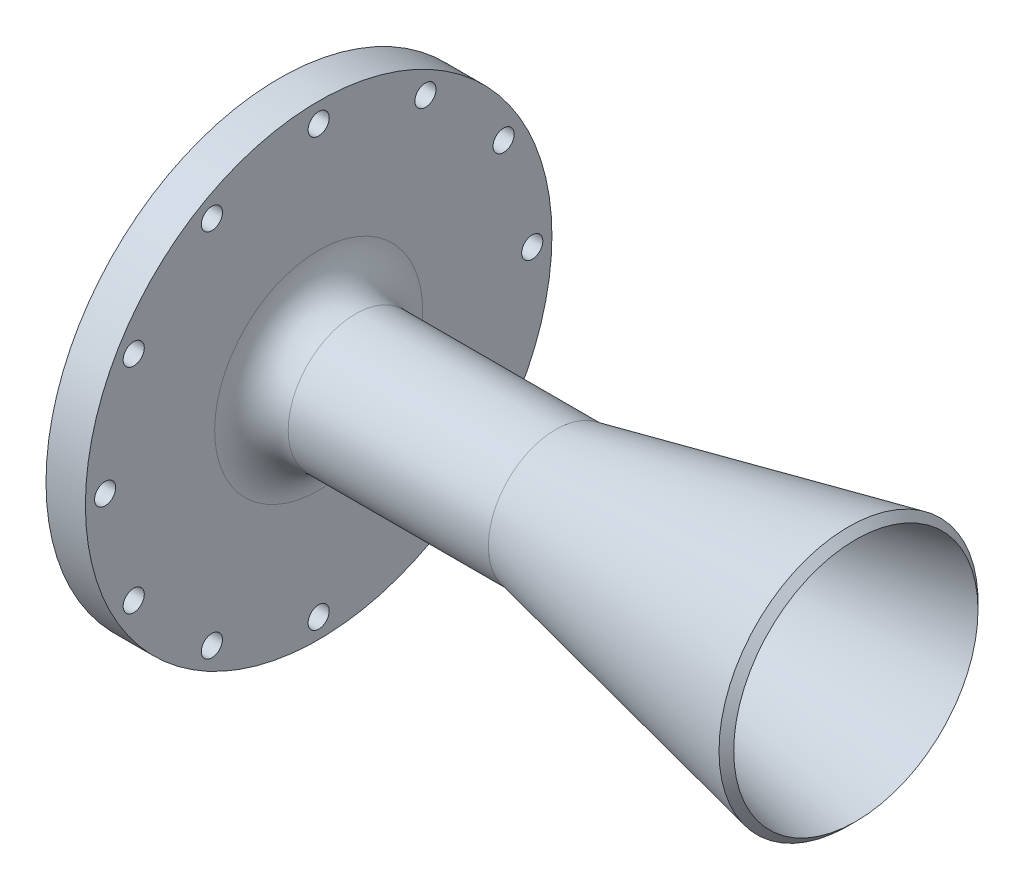
SolidWorks part; units mm, degrees
material "Stainless Steel (ferritic)"
ref_plane "Front Plane" through (0, 0, 0) normal (0, 0, 1) x (1, 0, 0)
ref_plane "Top Plane" through (0, 0, 0) normal (0, 1, 0) x (1, 0, 0)
ref_plane "Right Plane" through (0, 0, 0) normal (1, 0, 0) x (0, 0, -1)
sketch "Sketch2" plane through (0, 0, 0) normal (0, 0, 1) x (1, 0, 0)
  line L0 (0, 0) -> (165.0115, 0) construction
  line L1 (0, 20.5835) -> (0, 56.388)
  line L2 (0, 56.388) -> (9.525, 56.388)
  line L3 (9.525, 56.388) -> (9.525, 16.256)
  line L11 (66.8065, 16.256) -> (139.7, 31.75)
  line L17 (139.7, 31.75) -> (139.7, 29.5925)
  line L18 (60.325, 12.7208) -> (60.325, 14.351)
  line L19 (60.325, 14.351) -> (10.795, 14.351)
  line L20 (0, 20.5835) -> (10.795, 14.351)
  line L21 (60.325, 12.7208) -> (139.7, 29.5925)
  line L22 (9.525, 16.256) -> (66.8065, 16.256)
  dimension "D2" = 9.525
  dimension "D3" = 1.905
  dimension "D4" = 10.795
  dimension "D5" = 14.351
  dimension "D6" = 31.75
  dimension "D7" = 12
  dimension "D8" = 139.7
  dimension "D9" = 1.6302
  dimension "D10" = 30
  dimension "D11" = 56.388
  dimension "D12" = 49.53
revolve "Main Structure" add sketch "Sketch2" angle 360 about L0
sketch "Sketch4" plane through (0, 0, 0) normal (-1, 0, 0) x (0, 0, 1)
  circle A0 centre (0, 0) radius 51.6255 construction
  circle A1 centre (0, -51.6255) radius 2.146
  circle A2 centre (-25.8127, -44.709) radius 2.146
  circle A3 centre (-44.709, -25.8128) radius 2.146
  circle A4 centre (-51.6255, 0) radius 2.146
  circle A5 centre (-44.709, 25.8127) radius 2.146
  circle A6 centre (-25.8128, 44.709) radius 2.146
  circle A7 centre (0, 51.6255) radius 2.146
  circle A8 centre (25.8127, 44.709) radius 2.146
  circle A9 centre (44.709, 25.8128) radius 2.146
  circle A10 centre (51.6255, 0) radius 2.146
  circle A11 centre (44.709, -25.8127) radius 2.146
  circle A12 centre (25.8128, -44.709) radius 2.146
  point P29 (0, 0)
  dimension "D1" = 12
  dimension "D2" = 103.251
hole_wizard "Flange Holes" positions "Sketch7" profile "Sketch8" hole size "#7" standard "ANSI Inch" end condition up to next
sketch "Sketch7" plane through (0, 0, 0) normal (-1, 0, 0) x (0, 0, 1)
  point P0 (0, -51.6255)
  point P3 (-25.8127, -44.709)
  point P6 (-44.709, -25.8128)
  point P9 (-51.6255, 0)
  point P12 (-44.709, 25.8127)
  point P15 (-25.8128, 44.709)
  point P18 (0, 51.6255)
  point P21 (25.8127, 44.709)
  point P24 (44.709, 25.8128)
  point P27 (51.6255, 0)
  point P30 (44.709, -25.8127)
  point P33 (25.8128, -44.709)
sketch "Sketch8" plane through (0, -51.6255, 0) normal (0, 1, 0) x (0, 0, 1)
  line L0 (0, 0) -> (0, 9.525)
  line L1 (0, 9.525) -> (2.5527, 9.525)
  line L2 (2.5527, 9.525) -> (2.5527, 0)
  line L5 (2.5527, 0) -> (0, 0)
  line L11 (0, -6.35) -> (0, 107.95) construction
  dimension "Thru Hole Dia." = 5.1054
  dimension "Thru Hole Depth" = 9.525
sketch "Sketch9" plane through (0, 0, 0) normal (-1, 0, 0) x (0, 0, 1)
  line L0 (0, 0) -> (-67.6727, 18.1329) construction
  line L1 (0, 0) -> (-51.6255, 0) construction
  circle A0 centre (0, 0) radius 51.6255 construction
  circle A1 centre (-49.8664, 13.3617) radius 2.9451
  circle A2 centre (49.8664, -13.3617) radius 2.9451
  point P14 (0, 0)
  dimension "D1" = 15
  dimension "D2" = 2
hole_wizard "Dowel Holes" positions "Sketch10" profile "Sketch11" hole size "3/16" standard "ANSI Inch"
sketch "Sketch10" plane through (0, 0, 0) normal (-1, 0, 0) x (0, 0, 1)
  point P0 (49.8664, -13.3617)
  point P3 (-49.8664, 13.3617)
sketch "Sketch11" plane through (0, -13.3617, 49.8664) normal (0, 1, 0) x (0, 0, 1)
  line L0 (0, 0) -> (0, 7.7808)
  line L1 (0, 7.7808) -> (2.3812, 6.35)
  line L2 (2.3812, 6.35) -> (2.3812, 0)
  line L5 (2.3812, 0) -> (0, 0)
  line L10 (0, 7.7808) -> (-2.3812, 6.35) construction
  line L11 (0, -6.35) -> (0, 107.95) construction
  dimension "Hole Dia." = 4.7625
  dimension "Hole Depth" = 6.35
  dimension "Drill Angle" = 118
fillet "Fillet1" radius 8.89 1 edges at (9.525, 0, 16.256)
sketch "Sketch13" plane through (0, 0, 0) normal (0, 1, 0) x (1, 0, 0)
  line L0 (0, 36) -> (3.1496, 0)
  line L1 (0, 56.388) -> (0, -56.388) construction
  line L2 (3.1496, 0) -> (0, 0)
  line L3 (0, 0) -> (0, 36)
  dimension "D1" = 36
  dimension "D2" = 5
revolve "Cut-Revolve1" cut sketch "Sketch13" angle 360 about L2
chamfer "Chamfer1" distance 2.54 angle 45 1 edges at (139.7, 0, 31.75) first distance on face at (139.7, 0, 31.75)
